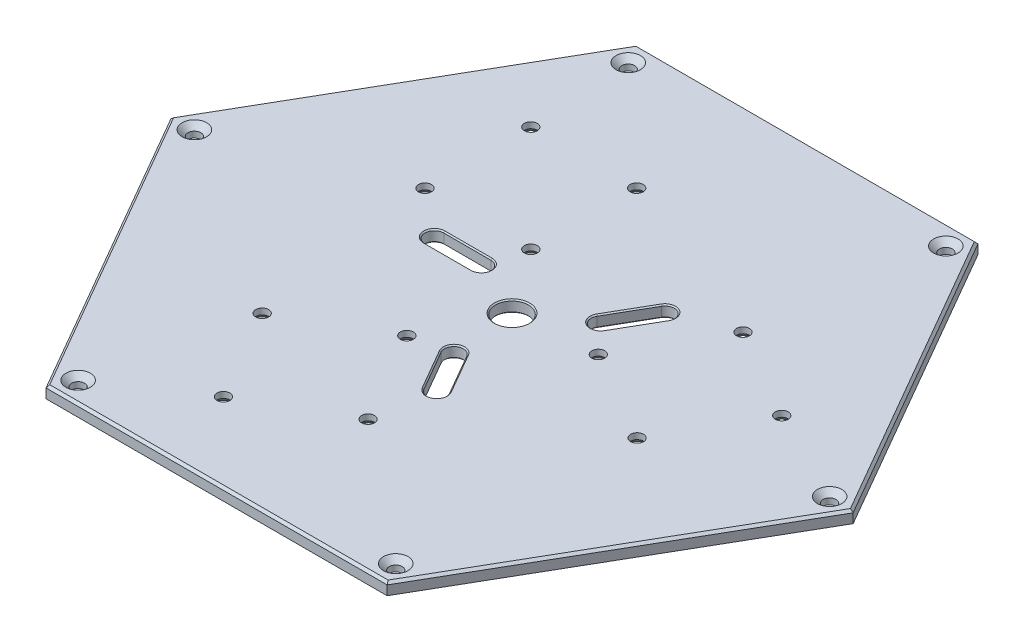
SolidWorks part; units mm, degrees
material "6061-T6 (SS)"
ref_plane "Front Plane" through (0, 0, 0) normal (0, 0, 1) x (1, 0, 0)
ref_plane "Top Plane" through (0, 0, 0) normal (0, 1, 0) x (1, 0, 0)
ref_plane "Right Plane" through (0, 0, 0) normal (1, 0, 0) x (0, 0, -1)
sketch "Sketch1" plane through (0, 0, 0) normal (0, 1, 0) x (1, 0, 0)
  line L1 (72.5, 125.5737) -> (-72.5, 125.5737)
  line L2 (-72.5, 125.5737) -> (-145, 0)
  line L3 (-145, 0) -> (-72.5, -125.5737)
  line L4 (-72.5, -125.5737) -> (72.5, -125.5737)
  line L5 (72.5, -125.5737) -> (145, 0)
  line L6 (145, 0) -> (72.5, 125.5737)
  circle A0 centre (0, 0) radius 125.5737 construction
  dimension "D1" = 145
extrude "Boss-Extrude1" add sketch "Sketch1" along normal blind 5
sketch "Sketch2" plane through (0, 0, 0) normal (0, 1, 0) x (1, 0, 0)
  line L0 (0, 0) -> (108.75, 62.7868) construction
  line L1 (145, 0) -> (72.5, 125.5737) construction
  line L2 (75.5513, 30.8586) -> (53.0513, -8.1125) construction
  line L3 (66.5368, -29.7548) -> (27.5657, -7.2548) construction
  line L6 (33.5657, 3.1375) -> (72.5368, -19.3625) construction
  line L7 (72.5368, -19.3625) -> (95.0368, 19.6086) construction
  line L8 (95.0368, 19.6086) -> (56.0657, 42.1086) construction
  line L9 (56.0657, 42.1086) -> (33.5657, 3.1375) construction
  line L10 (-14.0657, -30.6375) -> (-53.0368, -53.1375) construction
  line L11 (8.4343, -69.6086) -> (-14.0657, -30.6375) construction
  line L12 (-30.5368, -92.1086) -> (8.4343, -69.6086) construction
  line L13 (-53.0368, -53.1375) -> (-30.5368, -92.1086) construction
  line L14 (-19.5, 27.5) -> (-19.5, 72.5) construction
  line L15 (-64.5, 27.5) -> (-19.5, 27.5) construction
  line L16 (-64.5, 72.5) -> (-64.5, 27.5) construction
  line L17 (-19.5, 72.5) -> (-64.5, 72.5) construction
  line L19 (53.0513, -8.1125) -> (43.3013, -25) construction
  line L21 (108.75, -62.7868) -> (0, 0) construction
  line L22 (72.5, -125.5737) -> (145, 0) construction
  point P9 (47.0513, -18.5048)
  point P18 (33.5657, 3.1375)
  point P19 (56.0657, 42.1086)
  point P20 (95.0368, 19.6086)
  point P21 (72.5368, -19.3625)
  point P31 (0, 0)
  dimension "D1" = 45
  dimension "D2" = 45
  dimension "D4" = 7.5
  dimension "D5" = 12
  dimension "D6" = 50
  dimension "D3" = 3
sketch "Sketch5" plane through (0, 5, 0) normal (0, 1, 0) x (1, 0, 0)
  circle A0 centre (0, 0) radius 7
  dimension "D1" = 14
extrude "Cut-Extrude1" cut sketch "Sketch5" against normal through all
hole_wizard "CSK for M5 Flat Head Machine Screw1" positions "Sketch7" profile "Sketch6" countersink size "M5" standard "ANSI Metric" end condition through all
sketch "Sketch7" plane through (0, 0, 0) normal (0, -1, 0) x (-1, 0, 0)
  point P0 (64.5, 27.5)
  point P3 (19.5, 27.5)
  point P6 (19.5, 72.5)
  point P9 (64.5, 72.5)
  point P12 (-33.5657, 3.1375)
  point P15 (-72.5368, -19.3625)
  point P18 (-95.0368, 19.6086)
  point P21 (-56.0657, 42.1086)
  point P24 (14.0657, -30.6375)
  point P27 (-8.4343, -69.6086)
  point P30 (30.5368, -92.1086)
  point P33 (53.0368, -53.1375)
sketch "Sketch6" plane through (-64.5, 0, -27.5) normal (1, 0, 0) x (0, 0, -1)
  line L0 (0, 0) -> (0, 5)
  line L1 (0, 5) -> (2.75, 5)
  line L2 (2.75, 5) -> (2.75, 2.45)
  line L3 (2.75, 2.45) -> (5.2, 0)
  line L5 (5.2, 0) -> (0, 0)
  line L6 (-2.75, 2.45) -> (-5.2, 0) construction
  line L11 (0, -6.35) -> (0, 107.95) construction
  dimension "Thru Hole Dia." = 5.5
  dimension "Thru Hole Depth" = 5
  dimension "Near C'Sink Dia." = 10.4
  dimension "Near C'Sink Angle" = 90
sketch "Sketch9" plane through (0, 0, 0) normal (0, -1, 0) x (1, 0, 0)
  line L0 (32.2093, -32.7881) -> (22.2093, -15.4676) construction
  line L1 (28.7452, -34.7881) -> (18.7452, -17.4676)
  line L2 (35.6734, -30.7881) -> (25.6734, -13.4676)
  line L3 (19.7093, -11.1375) -> (42.2093, -50.1086) construction
  line L4 (95.0368, -19.6086) -> (56.0657, -42.1086) construction
  line L5 (33.5657, -3.1375) -> (72.5368, 19.3625) construction
  line L6 (56.0657, -42.1086) -> (33.5657, -3.1375) construction
  line L7 (-44.5, -11.5) -> (-24.5, -11.5) construction
  line L8 (-44.5, -7.5) -> (-24.5, -7.5)
  line L9 (-44.5, -15.5) -> (-24.5, -15.5)
  line L10 (12.2907, 44.2881) -> (2.2907, 26.9676) construction
  line L11 (15.7548, 42.2881) -> (5.7548, 24.9676)
  line L12 (8.8266, 46.2881) -> (-1.1734, 28.9676)
  arc A0 (28.7452, -34.7881) -> (35.6734, -30.7881) centre (32.2093, -32.7881) ccw
  arc A1 (25.6734, -13.4676) -> (18.7452, -17.4676) centre (22.2093, -15.4676) ccw
  arc A2 (-44.5, -7.5) -> (-44.5, -15.5) centre (-44.5, -11.5) ccw
  arc A3 (-24.5, -15.5) -> (-24.5, -7.5) centre (-24.5, -11.5) ccw
  arc A4 (15.7548, 42.2881) -> (8.8266, 46.2881) centre (12.2907, 44.2881) ccw
  arc A5 (-1.1734, 28.9676) -> (5.7548, 24.9676) centre (2.2907, 26.9676) ccw
  point P2 (27.2093, -24.1279)
  point P19 (-34.5, -11.5)
  point P26 (7.2907, 35.6279)
  point P31 (0, 0)
  dimension "D1" = 16
  dimension "D2" = 8
  dimension "D3" = 20
  dimension "D5" = 30
  dimension "D4" = 3
extrude "Cut-Extrude3" cut sketch "Sketch9" against normal through all
sketch "Sketch10" plane through (0, 5, 0) normal (0, 1, 0) x (1, 0, 0)
  line L0 (145, 0) -> (0, 0) construction
  point P4 (135, 0)
  point P7 (67.5, -116.9134)
  point P8 (-67.5, -116.9134)
  point P9 (-135, 0)
  point P10 (-67.5, 116.9134)
  point P11 (67.5, 116.9134)
  point P12 (0, 0)
  dimension "D2" = 10
  dimension "D1" = 6
hole_wizard "CSK for M5 Flat Head Machine Screw2" positions "Sketch14" profile "Sketch13" countersink size "M5" standard "ANSI Metric"
sketch "Sketch14" plane through (0, 5, 0) normal (0, 1, 0) x (1, 0, 0)
  point P0 (-135, 0)
  point P3 (-67.5, -116.9134)
  point P6 (67.5, -116.9134)
  point P9 (135, 0)
  point P12 (67.5, 116.9134)
  point P15 (-67.5, 116.9134)
sketch "Sketch13" plane through (-135, 5, 0) normal (1, 0, 0) x (0, 0, 1)
  line L0 (0, 0) -> (0, 11.6524)
  line L1 (0, 11.6524) -> (2.75, 10)
  line L2 (2.75, 10) -> (2.75, 2.45)
  line L3 (2.75, 2.45) -> (5.2, 0)
  line L5 (5.2, 0) -> (0, 0)
  line L6 (-2.75, 2.45) -> (-5.2, 0) construction
  line L10 (0, 11.6524) -> (-2.75, 10) construction
  line L11 (0, -6.35) -> (0, 107.95) construction
  dimension "Hole Dia." = 5.5
  dimension "Hole Depth" = 10
  dimension "Near C'Sink Dia." = 10.4
  dimension "Near C'Sink Angle" = 90
  dimension "Drill Angle" = 118
chamfer "Chamfer1" distance 0.5 angle 45 24 edges at (-34.5, 0, -15.5) (-20.5, 0, -11.5) (-48.5, 0, -11.5) (-34.5, 0, -7.5) (23.7452, 0, -26.1279) (34.2093, 0, -36.2522) (20.2093, 0, -12.0035) (30.6734, 0, -22.1279) (3.8266, 0, 37.6279) (0.2907, 0, 23.5035) (14.2907, 0, 47.7522) (10.7548, 0, 33.6279) (-34.5, 5, -15.5) (-20.5, 5, -11.5) (-48.5, 5, -11.5) (-34.5, 5, -7.5) (23.7452, 5, -26.1279) (34.2093, 5, -36.2522) (20.2093, 5, -12.0035) (30.6734, 5, -22.1279) (3.8266, 5, 37.6279) (0.2907, 5, 23.5035) (14.2907, 5, 47.7522) (10.7548, 5, 33.6279)
sketch "Sketch8" plane through (0, 0, 0) normal (0, -1, 0) x (1, 0, 0)
  line L0 (104.25, 70.5811) -> (113.25, 54.9926)
  line L1 (104.25, 70.5811) -> (66.9471, 49.0442)
  line L2 (113.25, 54.9926) -> (75.9471, 33.4558)
  line L3 (66.9471, 49.0442) -> (75.9471, 33.4558)
  line L4 (72.5, 125.5737) -> (145, 0) construction
  line L5 (108.75, 62.7868) -> (0, 0) construction
  line L7 (9, -125.5737) -> (-9, -125.5737)
  line L8 (9, -125.5737) -> (9, -82.5)
  line L9 (-9, -125.5737) -> (-9, -82.5)
  line L10 (9, -82.5) -> (-9, -82.5)
  line L11 (-113.25, 54.9926) -> (-104.25, 70.5811)
  line L12 (-113.25, 54.9926) -> (-75.9471, 33.4558)
  line L13 (-104.25, 70.5811) -> (-66.9471, 49.0442)
  line L14 (-75.9471, 33.4558) -> (-66.9471, 49.0442)
  circle A0 centre (0, 0) radius 7 construction
  point P6 (108.75, 62.7868)
  point P22 (0, 0)
  dimension "D1" = 18
  dimension "D2" = 10
  dimension "D3" = 3
extrude "Cut-Extrude2" [suppressed] cut sketch "Sketch8" against normal through all
chamfer "Chamfer3" distance 0.5 angle 45 2 edges at (0, 5, 7) (0, 0, 7)
chamfer "Chamfer4" distance 1 angle 45 6 edges at (0, 5, 125.5737) (108.75, 5, 62.7868) (108.75, 5, -62.7868) (0, 5, -125.5737) (-108.75, 5, -62.7868) (-108.75, 5, 62.7868)
